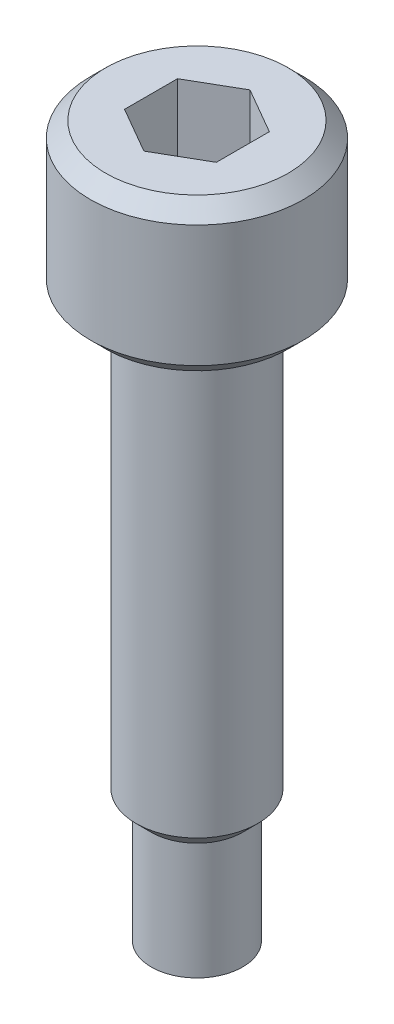
SolidWorks part; units mm, degrees
ref_plane "Front Plane" through (0, 0, 0) normal (0, 0, 1) x (1, 0, 0)
ref_plane "Top Plane" through (0, 0, 0) normal (0, 1, 0) x (1, 0, 0)
ref_plane "Right Plane" through (0, 0, 0) normal (1, 0, 0) x (0, 0, -1)
sketch "Sketch1" plane through (0, 0, 0) normal (0, 0, 1) x (1, 0, 0)
  line L0 (0, 0) -> (4.5, 0)
  line L1 (4.5, 0) -> (4.5, 11.5)
  line L2 (4.5, 11.5) -> (6, 11.5)
  line L3 (6, 11.5) -> (6, 55)
  line L4 (6, 55) -> (10.5, 55)
  line L5 (10.5, 55) -> (10.5, 70)
  line L6 (10.5, 70) -> (0, 70)
  line L7 (0, 70) -> (0, 0)
  dimension "D1" = 11.5
  dimension "D2" = 70
  dimension "D3" = 15
  dimension "D4" = 4.5
  dimension "D5" = 6
  dimension "D6" = 10.5
revolve "Revolve1" add sketch "Sketch1" angle 360 about L7
chamfer "Chamfer1" distance 1.5 angle 45 3 edges at (-6, 11.5, 0) (-10.5, 55, 0) (-10.5, 70, 0)
sketch "Sketch2" plane through (0, 70, 0) normal (0, 1, 0) x (1, 0, 0)
  line L1 (0, 5.2246) -> (-4.5247, 2.6123)
  line L2 (-4.5247, 2.6123) -> (-4.5247, -2.6123)
  line L3 (-4.5247, -2.6123) -> (0, -5.2246)
  line L4 (0, -5.2246) -> (4.5247, -2.6123)
  line L5 (4.5247, -2.6123) -> (4.5247, 2.6123)
  line L6 (4.5247, 2.6123) -> (0, 5.2246)
  circle A0 centre (0, 0) radius 4.5247 construction
  dimension "D1" = 9.0493
extrude "Cut-Extrude1" cut sketch "Sketch2" against normal blind 8
